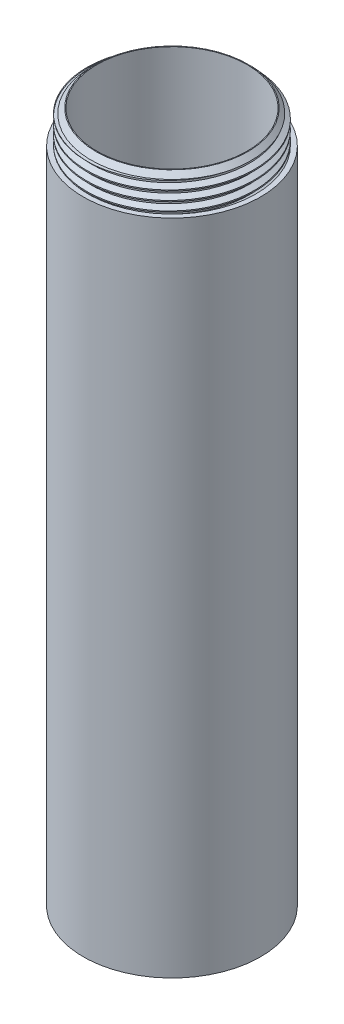
SolidWorks part; units mm, degrees
ref_plane "Front Plane" through (0, 0, 0) normal (0, 0, 1) x (1, 0, 0)
ref_plane "Top Plane" through (0, 0, 0) normal (0, 1, 0) x (1, 0, 0)
ref_plane "Right Plane" through (0, 0, 0) normal (1, 0, 0) x (0, 0, -1)
sketch "Sketch1" plane through (0, 0, 0) normal (0, 1, 0) x (1, 0, 0)
  circle A0 centre (0, 0) radius 17.4625
  circle A1 centre (0, 0) radius 20.6375
  dimension "D1" = 34.925
  dimension "D2" = 3.175
extrude "Boss-Extrude1" add sketch "Sketch1" along normal blind 158.75
sketch "Sketch2" plane through (0, 0, 0) normal (0, -1, 0) x (-1, 0, 0)
  circle A0 centre (0, 0) radius 20.6375
  circle A1 centre (0, 0) radius 20.6375 construction
extrude "Boss-Extrude2" add sketch "Sketch2" along normal blind 2
sketch "Sketch13" plane through (0, 158.75, 0) normal (0, 1, 0) x (1, 0, 0)
  line L0 (-19.4945, 0) -> (-17.4625, 0) construction
  circle A0 centre (0, 0) radius 20.6375
  circle A1 centre (0, 0) radius 19.4945
  circle A2 centre (0, 0) radius 17.4625 construction
  circle A3 centre (0, 0) radius 20.6375 construction
  dimension "D1" = 2.032
extrude "Cut-Extrude1" cut sketch "Sketch13" against normal blind 7.62
thread "Thread1" pitch 2.1167 method cut profile "Thread Profile1" start angle 0, offset 2.54, length 0, pitch 2.1167, diameter 38.989
ref_plane "Plane1" through (-19.4945, 161.29, 0) normal (0, 0, 1) x (-1, 0, 0)
sketch "Thread Profile1" plane through (-19.4945, 161.29, 0) normal (0, 0, 1) x (-1, 0, 0)
  line L0 (0, 0) -> (0, 2.1167) construction
  line L11 (0, 0) -> (0, 1.8521)
  line L12 (0, 1.8521) -> (-1.1457, 1.1906)
  line L13 (-1.1457, 1.1906) -> (-1.1457, 0.6615)
  line L15 (-1.1457, 0.6615) -> (0, 0)
  line L17 (-1.1457, 0.926) -> (0, 0.926) construction
  point P2 (0, 0)
  dimension "Pitch" = 2.1167
  dimension "Profile_Angle" = 60
  dimension "Profile_Land" = 0.5292
  dimension "Profile_Height" = 1.1457
sketch "Sketch16" plane through (0, 0, 0) normal (0, 0, 1) x (1, 0, 0)
  line L0 (0, 0) -> (0, 156.9021) construction
  line L1 (-16.51, 159.893) -> (-18.796, 157.607)
  line L2 (-18.796, 157.607) -> (-21.615, 157.607)
  line L3 (-21.615, 157.607) -> (-21.615, 159.893)
  line L4 (-21.615, 159.893) -> (-16.51, 159.893)
  line L6 (20.6375, 151.13) -> (-20.6375, 151.13) construction
  dimension "D1" = 45
  dimension "D2" = 16.51
  dimension "D3" = 2.286
  dimension "D4" = 6.477
revolve "Cut-Revolve1" cut sketch "Sketch16" angle 360 about L0
